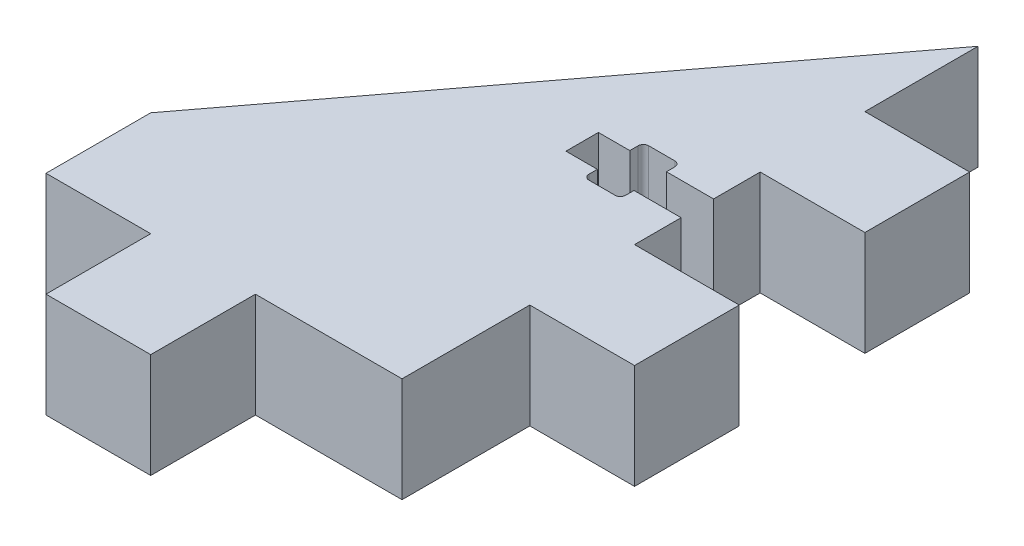
SolidWorks part; units mm, degrees
ref_plane "Front Plane" through (0, 0, 0) normal (0, 0, 1) x (1, 0, 0)
ref_plane "Top Plane" through (0, 0, 0) normal (0, 1, 0) x (1, 0, 0)
ref_plane "Right Plane" through (0, 0, 0) normal (1, 0, 0) x (0, 0, -1)
sketch "Sketch1" plane through (0, 0, 0) normal (0, 1, 0) x (1, 0, 0)
  line L0 (0, 0) -> (-14, 0)
  line L1 (-14, 0) -> (-14, -10)
  line L2 (-14, -10) -> (-24, -10)
  line L3 (-24, -10) -> (-24, 0)
  line L4 (-24, 0) -> (-34, 0)
  line L5 (-34, 0) -> (-34, 10)
  line L6 (-34, 10) -> (0, 55)
  line L7 (0, 55) -> (0, 44.2)
  line L8 (0, 44.2) -> (10, 44.2)
  line L9 (10, 44.2) -> (10, 34.2)
  line L10 (10, 34.2) -> (0, 34.2)
  line L11 (0, 34.2) -> (0, 22.2)
  line L12 (-24, 0) -> (-14, 0) construction
  line L13 (-19, 0) -> (-19, -10) construction
  line L14 (0, 17.2) -> (0, 12.2) construction
  line L15 (5, 12.2) -> (5, 21.2) construction
  line L16 (10, 34.2) -> (10, 22.2) construction
  line L17 (0, 28.2) -> (10, 28.2) construction
  line L24 (0, 22.2) -> (10, 22.2)
  line L25 (10, 22.2) -> (10, 12.2)
  line L26 (10, 12.2) -> (0, 12.2)
  line L27 (0, 12.2) -> (0, 0)
  line L32 (10, 39.2) -> (0, 39.2) construction
  line L33 (0, 39.2) -> (0, 34.2) construction
  line L34 (10, 17.2) -> (0, 17.2) construction
  line L35 (0, 17.2) -> (0, 22.2) construction
  dimension "D1" = 10
  dimension "D2" = 10
  dimension "D3" = 10
  dimension "D7" = 10
  dimension "D8" = 10
  dimension "D10" = 10
  dimension "D11" = 10
  dimension "D12" = 10
  dimension "D9" = 55
  dimension "D4" = 22
  dimension "D6" = 24
  dimension "D5" = 28.2
extrude "Boss-Extrude1" add sketch "Sketch1" along normal blind 10
sketch "Sketch2" [suppressed] plane through (0, 8, 0) normal (0, 1, 0) x (1, 0, 0)
  line L0 (0, 29.9) -> (0, 25.9) construction
  line L1 (0, 27.9) -> (-7.2, 27.9) construction
  line L2 (-7.2, 25.9) -> (-7.2, 29.9) construction
  line L3 (7.5, 36.4) -> (7.5, 20.4) construction
  line L4 (0, 36.4) -> (7.5, 36.4) construction
  line L5 (0, 27.9) -> (7.5, 27.9) construction
sketch "Sketch3" plane through (0, 10, 0) normal (0, 1, 0) x (1, 0, 0)
  line L0 (0, 28.2) -> (-11, 28.2) construction
  line L1 (0, 22.2) -> (0, 34.2) construction
  line L2 (-11, 29.75) -> (-8, 29.75)
  line L3 (-8, 29.75) -> (-8, 30.55)
  line L4 (-7.5, 31.05) -> (-5, 31.05)
  line L5 (-4.5, 30.55) -> (-4.5, 29.75)
  line L6 (-4.5, 29.75) -> (0, 29.75)
  line L7 (0, 29.75) -> (0, 26.65)
  line L8 (-11, 29.75) -> (-11, 26.65)
  line L9 (-4.5, 26.65) -> (0, 26.65)
  line L10 (-4.5, 25.85) -> (-4.5, 26.65)
  line L11 (-7.5, 25.35) -> (-5, 25.35)
  line L12 (-8, 26.65) -> (-8, 25.85)
  line L13 (-11, 26.65) -> (-8, 26.65)
  arc A0 (-8, 30.55) -> (-7.5, 31.05) centre (-7.5, 30.55) cw
  arc A1 (-5, 31.05) -> (-4.5, 30.55) centre (-5, 30.55) cw
  arc A2 (-5, 25.35) -> (-4.5, 25.85) centre (-5, 25.85) ccw
  arc A3 (-8, 25.85) -> (-7.5, 25.35) centre (-7.5, 25.85) ccw
  point P12 (-8, 31.05)
  point P15 (-4.5, 31.05)
  point P26 (-4.5, 25.35)
  point P27 (-8, 25.35)
  dimension "D7" = 0.5
  dimension "D1" = 11
  dimension "D3" = 1.55
  dimension "D2" = 8
  dimension "D4" = 3.5
  dimension "D5" = 2.85
  dimension "D6" = 1.55
extrude "Cut-Extrude1" cut sketch "Sketch3" against normal through all
equation "\"Y-ROD-SPACING\"=75"
equation "\"Y-BED-OFFSET\"=2"
equation "\"Y-BED-ROD-INSET\"=3.5"
equation "\"T-SLOT-NUT-FILLET-RADIUS\"=0.5"
equation "\"T-SLOT-SCREW-SHAFT-RADIUS\"=1.55"
equation "\"T-SLOT-SCREW-SHAFT-CUTOUT-LENGTH\"=11"
equation "\"T-SLOT-NUT-DEPTH\"=3.5"
equation "\"T-SLOT-NUT-WIDTH\"=2.85"
equation "\"T-SLOT-NUT-END-DISTANCE\"=8"
equation "\"ACRYLIC-TAB-CUTOUT-SIZE\"=\"ACRYLIC-THICKNESS\"+\"ACRYLIC-TAB-TOLERANCE\"*2"
equation "\"ACRYLIC-TAB-WIDTH\"=\"ACRYLIC-THICKNESS\""
equation "\"ACRYLIC-M3-HOLE\"=2.9"
equation "\"SMOOTHROD-CAP-SCREW-DISTANCE\"=20"
equation "\"FRAME-WIDTH-INNER\"=370"
equation "\"NEMA17-HOLE-SPACING\"=31"
equation "\"NEMA17-CENTRAL-CUTOUT\"=22.5"
equation "\"D3@Sketch1\"=\"ACRYLIC-TAB-WIDTH\""
equation "\"D12@Sketch1\"=\"ACRYLIC-TAB-WIDTH\""
equation "\"D2@Sketch1\"=\"ACRYLIC-TAB-WIDTH\""
equation "\"D11@Sketch1\"=\"ACRYLIC-TAB-WIDTH\""
equation "\"D1@Sketch1\"=\"ACRYLIC-TAB-WIDTH\""
equation "\"D10@Sketch1\"=\"ACRYLIC-TAB-WIDTH\""
equation "\"Z-BRACKET-REACH\"=55"
equation "\"D9@Sketch1\"=\"Z-BRACKET-REACH\""
equation "\"D6@Sketch3\"=\"T-SLOT-SCREW-SHAFT-RADIUS\""
equation "\"D3@Sketch3\"=\"T-SLOT-SCREW-SHAFT-RADIUS\""
equation "\"D4@Sketch3\"=\"T-SLOT-NUT-DEPTH\""
equation "\"D7@Sketch3\"=\"T-SLOT-NUT-FILLET-RADIUS\""
equation "\"D1@Sketch3\"=\"T-SLOT-SCREW-SHAFT-CUTOUT-LENGTH\""
equation "\"D5@Sketch3\"=\"T-SLOT-NUT-WIDTH\""
equation "\"D2@Sketch3\"=\"T-SLOT-NUT-END-DISTANCE\""
equation "\"X-ROD-SPACING\"=45"
equation "\"Z-ROD-SPACING\"=17.5"
equation "\"ACRYLIC-THICKNESS\"=10"
equation "\"ACRYLIC-THICKNESS2\"=4.5"
equation "\"TOP-BRACKET-SPACING\"=40"
equation "\"SMOOTHROD-X-LENGTH\"=350"
equation "\"SMOOTHROD-Y-LENGTH\"=350"
equation "\"SMOOTHROD-Z-LENGTH\"=350"
equation "\"SMOOTHROD-TIGHTENING-HEADROOM\"=.25"
equation "\"LEADSCREW-Z-LENGTH\"=300"
equation "\"SCREW-LENGTH-FRAME\"=\"ACRYLIC-THICKNESS\" + 10"
equation "\"SCREW-HEAD-RADIUS\"=6"
equation "\"PRINTED-X-SMOOTHROD-DIAMETER\"=8.8"
equation "\"PRINTED-X-SMOOTHROD-CUTOUT\"=10"
equation "\"PRINTED-X-BASE-HEIGHT\"=10"
equation "\"PRINTED-LM8UU-CUTOUT-SIZE\"=15.5"
equation "\"PRINTED-LM8UU-CUTOUT-LENGTH\"=24.5"
equation "\"PRINTED-X-IDLER-HEIGHT\"=16"
equation "\"PSU-MOUNTING-WIDTH\"=95"
equation "\"PSU-MOUNTING-HEIGHT\"=177"
equation "\"D1@Boss-Extrude1\"=\"ACRYLIC-THICKNESS\""
